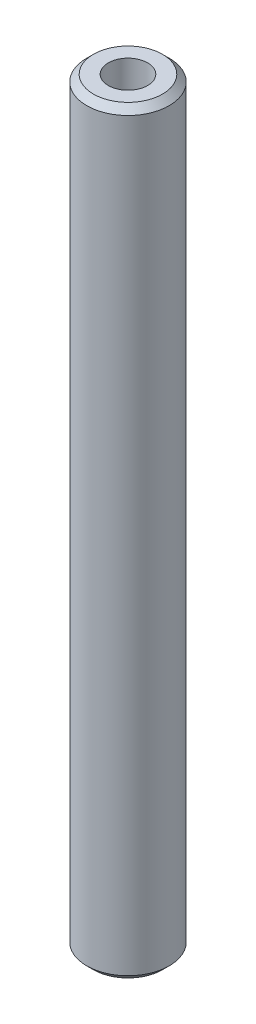
SolidWorks part; units mm, degrees
ref_plane "Front Plane" through (0, 0, 0) normal (0, 0, 1) x (1, 0, 0)
ref_plane "Top Plane" through (0, 0, 0) normal (0, 1, 0) x (1, 0, 0)
ref_plane "Right Plane" through (0, 0, 0) normal (1, 0, 0) x (0, 0, -1)
sketch "Sketch1" plane through (0, 0, 0) normal (0, 1, 0) x (1, 0, 0)
  circle A0 centre (0, 0) radius 5
  dimension "SHAFT_OD" = 10
extrude "Boss-Extrude1" add sketch "Sketch1" along normal blind 92.0167
sketch "Sketch2" plane through (0, 0, 0) normal (0, 1, 0) x (1, 0, 0)
  circle A0 centre (0, 0) radius 2.3886
  dimension "BORE_D" = 4.7772
extrude "Cut-Extrude1" cut sketch "Sketch2" along normal through all
chamfer "Chamfer1" distance 0.8104 angle 45 2 edges at (0, 92.0167, 5) (0, 0, 5)
